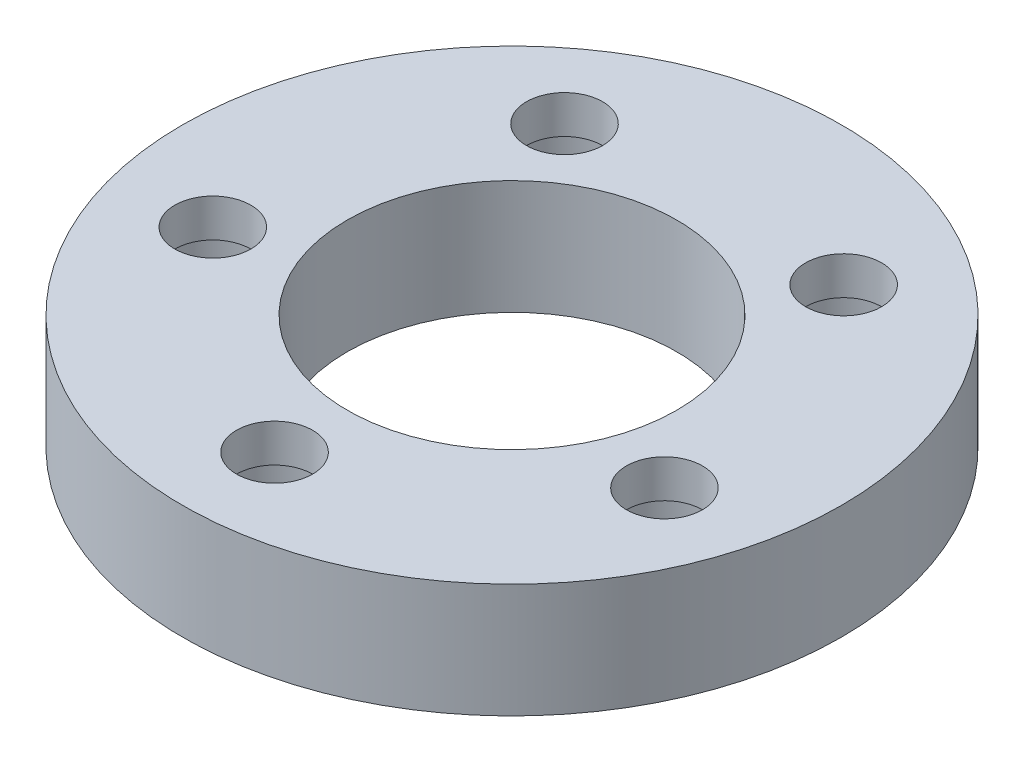
SolidWorks part; units mm, degrees
ref_plane "Front Plane" through (0, 0, 0) normal (0, 0, 1) x (1, 0, 0)
ref_plane "Top Plane" through (0, 0, 0) normal (0, 1, 0) x (1, 0, 0)
ref_plane "Right Plane" through (0, 0, 0) normal (1, 0, 0) x (0, 0, -1)
sketch "Sketch1" plane through (0, 0, 0) normal (0, 0, 1) x (1, 0, 0)
  line L0 (22, -25.3372) -> (11, -25.3372)
  line L2 (0, 18.6628) -> (0, 5.4128)
  line L3 (22, -25.3372) -> (11, -25.3372)
  line L4 (22, -25.3372) -> (22, -32.9572)
  line L5 (11, -18.3372) -> (11, -25.3372)
  line L6 (22, -32.9572) -> (11, -32.9572)
  line L7 (11, -25.3372) -> (11, -32.9572)
  ellipse E1 centre (11, -25.3372) end of major axis (0, -25.3372) minor radius 7 (11, -18.3372) -> (22, -25.3372) cw
  dimension "D1" = 7.62
revolve "Revolve1" add sketch "Sketch1" angle 360 about L2 region at (16.5, -29.1472, 0)
sketch "Sketch2" plane through (0, -32.9572, 0) normal (0, -1, 0) x (1, 0, 0)
  circle A0 centre (15.0742, 4.8979) radius 2.54
  circle A1 centre (0, 15.85) radius 2.54
  circle A2 centre (9.3164, -12.8229) radius 2.54
  circle A3 centre (-9.3164, -12.8229) radius 2.54
  circle A4 centre (-15.0742, 4.8979) radius 2.54
  point P0 (0, 0)
  point P16 (0, 0)
  dimension "D1" = 15.85
  dimension "D2" = 5
extrude "Cut-Extrude1" cut sketch "Sketch2" against normal through all
sketch "Sketch3" plane through (0, -32.9572, 0) normal (0, -1, 0) x (-1, 0, 0)
  circle A0 centre (0, -15.85) radius 3.9688
  circle A1 centre (-15.0742, -4.8979) radius 3.9688
  circle A2 centre (-9.3164, 12.8229) radius 3.9687
  circle A3 centre (9.3164, 12.8229) radius 3.9687
  circle A4 centre (15.0742, -4.8979) radius 3.9688
  point P13 (0, 0)
  dimension "D1" = 7.9375
  dimension "D2" = 5
extrude "Cut-Extrude2" cut sketch "Sketch3" against normal blind 5.08
